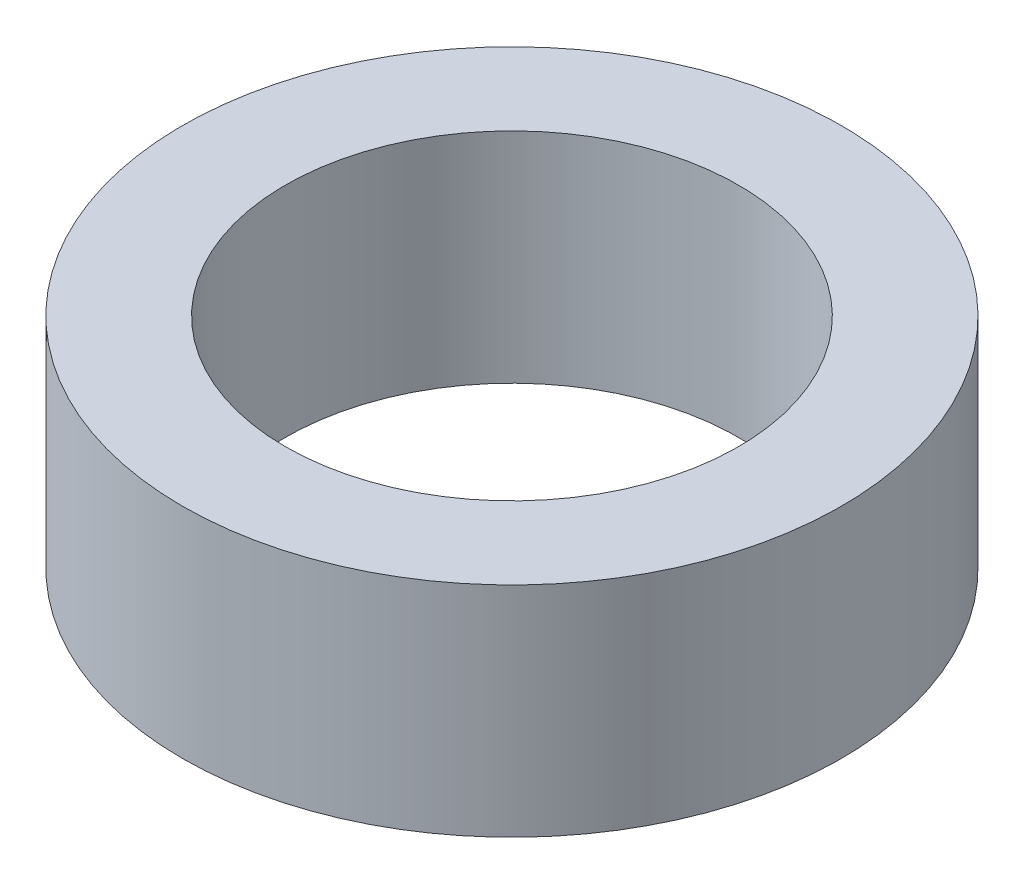
SolidWorks part; units mm, degrees
ref_plane "Front" through (0, 0, 0) normal (0, 0, 1) x (1, 0, 0)
ref_plane "Top" through (0, 0, 0) normal (0, 1, 0) x (1, 0, 0)
ref_plane "Right" through (0, 0, 0) normal (1, 0, 0) x (0, 0, -1)
sketch "Sketch1" plane through (0, 0, 0) normal (0, 1, 0) x (1, 0, 0)
  circle A0 centre (0, 0) radius 6.325
  circle A1 centre (0, 0) radius 9.2
extrude "Boss-Extrude1" add sketch "Sketch1" along normal blind 6.1
